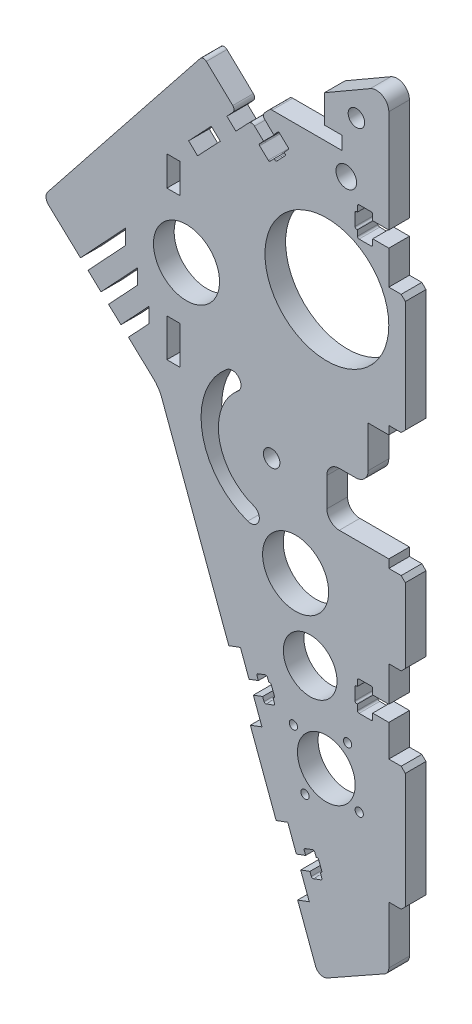
SolidWorks part; units mm, degrees
ref_plane "前视基准面" through (0, 0, 0) normal (0, 0, 1) x (1, 0, 0)
ref_plane "上视基准面" through (0, 0, 0) normal (0, 1, 0) x (1, 0, 0)
ref_plane "右视基准面" through (0, 0, 0) normal (1, 0, 0) x (0, 0, -1)
sketch "草图1" plane through (0, 0, 0) normal (0, 0, 1) x (1, 0, 0)
  line L0 (-10.2785, 30.2586) -> (-10.2785, 20.2586)
  line L1 (-13.2785, 20.2586) -> (-13.2785, 30.2586)
  line L2 (-10.2785, 20.2586) -> (-13.2785, 20.2586)
  line L3 (-13.2785, 30.2586) -> (-10.2785, 30.2586)
  line L4 (-10.2785, 63.2586) -> (-10.2785, 56.2586)
  line L5 (-13.2785, 56.2586) -> (-13.2785, 63.2586)
  line L6 (-13.2785, 56.2586) -> (-10.2785, 56.2586)
  line L7 (-10.2785, 63.2586) -> (-13.2785, 63.2586)
  line L8 (0.0584, 10.1694) -> (8.4478, 4.7272)
  line L9 (8.4478, 4.7272) -> (6.8151, 2.2104)
  line L10 (6.8151, 2.2104) -> (-1.5743, 7.6526)
  line L11 (-1.5743, 7.6526) -> (0.0584, 10.1694)
  line L12 (31.9832, -14.1164) -> (19.3992, -5.953)
  line L13 (19.3992, -5.953) -> (21.0318, -3.4362)
  line L14 (21.0318, -3.4362) -> (33.6159, -11.5996)
  line L15 (33.6159, -11.5996) -> (31.9832, -14.1164)
  line L16 (31.6744, 21.8979) -> (31.6744, -0.3482)
  line L17 (25.0756, 23.4255) -> (27.307, 24.5682)
  line L18 (6.079, 27.2365) -> (23.0089, 23.1784)
  line L19 (27.0417, -2.865) -> (3.747, 12.2464)
  line L20 (2.3797, 14.7633) -> (2.3797, 24.3191)
  line L21 (24.1101, 85.2586) -> (24.1101, 81.2586)
  line L22 (24.1101, 81.2586) -> (25.5101, 81.2586)
  line L23 (25.8101, 80.9586) -> (25.8101, 78.0586)
  line L24 (25.5101, 77.7586) -> (24.0601, 77.7586)
  line L25 (24.0601, 77.7586) -> (24.0601, 77.4586)
  line L26 (23.7601, 77.1586) -> (20.8601, 77.1586)
  line L27 (20.5601, 77.4586) -> (20.5601, 77.7586)
  line L28 (20.5601, 77.7586) -> (19.1101, 77.7586)
  line L29 (18.8101, 78.0586) -> (18.8101, 80.9586)
  line L30 (19.1101, 81.2586) -> (20.5101, 81.2586)
  line L31 (20.5101, 81.2586) -> (20.5101, 85.2586)
  line L32 (20.5101, 85.2586) -> (11.6643, 85.2586)
  line L33 (11.6643, 85.2586) -> (9.5983, 83.0749)
  line L34 (9.5983, 83.0749) -> (12.504, 80.3259)
  line L35 (12.504, 80.3259) -> (13.4662, 81.3429)
  line L36 (13.8903, 81.3547) -> (15.9969, 79.3617)
  line L37 (16.0087, 78.9376) -> (15.0122, 77.8843)
  line L38 (15.0122, 77.8843) -> (15.2301, 77.6781)
  line L39 (15.2419, 77.254) -> (13.2489, 75.1473)
  line L40 (12.8248, 75.1356) -> (12.6068, 75.3417)
  line L41 (12.6068, 75.3417) -> (11.6104, 74.2884)
  line L42 (11.1863, 74.2767) -> (9.0796, 76.2696)
  line L43 (9.0678, 76.6937) -> (10.03, 77.7108)
  line L44 (10.03, 77.7108) -> (7.1242, 80.4597)
  line L45 (7.1242, 80.4597) -> (3.3349, 76.4543)
  line L46 (3.3349, 76.4543) -> (1.1556, 78.516)
  line L47 (1.1556, 78.516) -> (3.2882, 80.7702)
  line L48 (3.2882, 80.7702) -> (-4.6274, 88.2586)
  line L49 (-4.6274, 88.2586) -> (-43.3726, 39.5134)
  line L50 (-43.3726, 39.5134) -> (-15.2785, 13.2991)
  line L51 (-15.2785, 13.2991) -> (23.442, -91.2586)
  line L52 (23.442, -91.2586) -> (40.3726, -81.7414)
  line L53 (40.3726, -81.7414) -> (40.3726, -66.7414)
  line L54 (40.3726, -66.7414) -> (43.3726, -66.7414)
  line L55 (43.3726, -66.7414) -> (43.3726, -36.7414)
  line L56 (43.3726, -36.7414) -> (40.3726, -36.7414)
  line L57 (40.3726, -36.7414) -> (40.3726, -16.7414)
  line L58 (40.3726, -16.7414) -> (43.3726, -16.7414)
  line L59 (43.3726, -16.7414) -> (43.3726, 3.2586)
  line L60 (43.3726, 3.2586) -> (40.3726, 3.2586)
  line L61 (40.3726, 3.2586) -> (40.3726, 33.2586)
  line L62 (40.3726, 33.2586) -> (43.3726, 33.2586)
  line L63 (43.3726, 33.2586) -> (43.3726, 63.2586)
  line L64 (43.3726, 63.2586) -> (40.3726, 63.2586)
  line L65 (40.3726, 63.2586) -> (40.3726, 91.2586)
  line L66 (40.3726, 91.2586) -> (26.0184, 89.2586)
  line L67 (26.0184, 89.2586) -> (26.0184, 88.2586)
  line L68 (26.0184, 88.2586) -> (29.0184, 88.2586)
  line L69 (29.0184, 88.2586) -> (29.0184, 85.2586)
  line L70 (29.0184, 85.2586) -> (24.1101, 85.2586)
  circle A0 centre (-0.6274, 42.9051) radius 1.5
  circle A1 centre (-16.6274, 42.9051) radius 1.5
  circle A2 centre (-8.6274, 42.9051) radius 2
  circle A3 centre (-8.6274, 33.4051) radius 1.5
  circle A4 centre (-8.6274, 52.4051) radius 1.5
  circle A5 centre (-3.3341, -7.5541) radius 1.5
  arc A6 (25.8101, 80.9586) -> (25.5101, 81.2586) centre (25.5101, 80.9586) ccw
  arc A7 (25.5101, 77.7586) -> (25.8101, 78.0586) centre (25.5101, 78.0586) ccw
  arc A8 (23.7601, 77.1586) -> (24.0601, 77.4586) centre (23.7601, 77.4586) ccw
  arc A9 (20.5601, 77.4586) -> (20.8601, 77.1586) centre (20.8601, 77.4586) ccw
  arc A10 (18.8101, 78.0586) -> (19.1101, 77.7586) centre (19.1101, 78.0586) ccw
  arc A11 (19.1101, 81.2586) -> (18.8101, 80.9586) centre (19.1101, 80.9586) ccw
  arc A12 (13.8903, 81.3547) -> (13.4662, 81.3429) centre (13.6841, 81.1367) ccw
  arc A13 (16.0087, 78.9376) -> (15.9969, 79.3617) centre (15.7907, 79.1438) ccw
  arc A14 (15.2419, 77.254) -> (15.2301, 77.6781) centre (15.0239, 77.4602) ccw
  arc A15 (12.8248, 75.1356) -> (13.2489, 75.1473) centre (13.031, 75.3535) ccw
  arc A16 (11.1863, 74.2767) -> (11.6104, 74.2884) centre (11.3924, 74.4946) ccw
  arc A17 (9.0678, 76.6937) -> (9.0796, 76.2696) centre (9.2858, 76.4876) ccw
  circle A18 centre (17.4285, -66.9467) radius 1.5
  circle A19 centre (7.9032, -39.3932) radius 1.5
  arc A20 (27.0417, -2.865) -> (31.6744, -0.3482) centre (28.6744, -0.3482) ccw
  arc A21 (31.6744, 21.8979) -> (27.307, 24.5682) centre (28.6744, 21.8979) ccw
  arc A22 (23.0089, 23.1784) -> (25.0756, 23.4255) centre (23.7082, 26.0958) ccw
  arc A23 (2.3797, 14.7633) -> (3.747, 12.2464) centre (5.3797, 14.7633) ccw
  arc A24 (6.079, 27.2365) -> (2.3797, 24.3191) centre (5.3797, 24.3191) ccw
extrude "凸台-拉伸1" add sketch "草图1" along normal blind 5
sketch "草图2" plane through (0, 0, 5) normal (0, 0, 1) x (1, 0, 0)
  line L0 (16.0872, 85.2586) -> (19.9404, 70.4407)
  line L1 (20.5101, 85.2586) -> (11.6643, 85.2586) construction
  line L2 (19.9404, 70.4407) -> (29.7785, 72.999)
  line L3 (29.7785, 72.999) -> (25.9385, 85.2586)
  line L4 (29.0184, 85.2586) -> (24.1101, 85.2586) construction
  line L5 (25.9385, 85.2586) -> (16.0872, 85.2586)
extrude "凸台-拉伸2" add sketch "草图2" against normal up to surface (5 mm away) up to face at (26.5075, -8.7763, 0)
sketch "草图3" plane through (0, 63.2586, 0) normal (0, 1, 0) x (1, 0, 0)
  line L4 (43.3726, 0) -> (40.3726, 0)
  line L5 (40.3726, 0) -> (40.3726, -5)
  line L6 (40.3726, -5) -> (43.3726, -5)
  line L7 (43.3726, -5) -> (43.3726, 0)
  line L8 (43.3726, 0) -> (40.3726, 0)
  line L9 (40.3726, 0) -> (40.3726, -5)
  line L10 (40.3726, -5) -> (43.3726, -5)
  line L11 (43.3726, -5) -> (43.3726, 0)
  dimension "D1" = 0
extrude "切除-拉伸1" cut sketch "草图3" against normal blind 6
extrude "切除-拉伸2" cut sketch "草图4" against normal blind 5
sketch "草图4" plane through (247.8726, 71.6626, 0) normal (0, 0, -1) x (-1, 0, 0)
  line L24 (211.5, -1.1166) -> (211.5, -2.5166)
  line L25 (207.5, -1.1166) -> (211.5, -1.1166)
  line L26 (207.5, 2.4834) -> (207.5, -1.1166)
  line L27 (211.5, 2.4834) -> (207.5, 2.4834)
  line L28 (211.5, 3.8834) -> (211.5, 2.4834)
  line L29 (214.7, 4.1834) -> (211.8, 4.1834)
  line L30 (215, 2.4334) -> (215, 3.8834)
  line L31 (215.3, 2.4334) -> (215, 2.4334)
  line L32 (215.6, -0.7666) -> (215.6, 2.1334)
  line L33 (215, -1.0666) -> (215.3, -1.0666)
  line L34 (215, -2.5166) -> (215, -1.0666)
  line L35 (211.8, -2.8166) -> (214.7, -2.8166)
  line L48 (215, -102.0074) -> (215, -100.5574)
  line L49 (211.8, -102.3074) -> (214.7, -102.3074)
  line L50 (211.5, -100.6074) -> (211.5, -102.0074)
  line L51 (207.5, -100.6074) -> (211.5, -100.6074)
  line L52 (207.5, -97.0074) -> (207.5, -100.6074)
  line L53 (211.5, -97.0074) -> (207.5, -97.0074)
  line L54 (211.5, -95.6074) -> (211.5, -97.0074)
  line L55 (214.7, -95.3074) -> (211.8, -95.3074)
  line L56 (215, -97.0574) -> (215, -95.6074)
  line L57 (215.3, -97.0574) -> (215, -97.0574)
  line L58 (215.6, -100.2574) -> (215.6, -97.3574)
  line L59 (215, -100.5574) -> (215.3, -100.5574)
  arc A12 (211.5, -2.5166) -> (211.8, -2.8166) centre (211.8, -2.5166) ccw
  arc A13 (211.8, 4.1834) -> (211.5, 3.8834) centre (211.8, 3.8834) ccw
  arc A14 (215, 3.8834) -> (214.7, 4.1834) centre (214.7, 3.8834) ccw
  arc A15 (215.6, 2.1334) -> (215.3, 2.4334) centre (215.3, 2.1334) ccw
  arc A16 (215.3, -1.0666) -> (215.6, -0.7666) centre (215.3, -0.7666) ccw
  arc A17 (214.7, -2.8166) -> (215, -2.5166) centre (214.7, -2.5166) ccw
  arc A24 (214.7, -102.3074) -> (215, -102.0074) centre (214.7, -102.0074) ccw
  arc A25 (211.5, -102.0074) -> (211.8, -102.3074) centre (211.8, -102.0074) ccw
  arc A26 (211.8, -95.3074) -> (211.5, -95.6074) centre (211.8, -95.6074) ccw
  arc A27 (215, -95.6074) -> (214.7, -95.3074) centre (214.7, -95.6074) ccw
  arc A28 (215.6, -97.3574) -> (215.3, -97.0574) centre (215.3, -97.3574) ccw
  arc A29 (215.3, -100.5574) -> (215.6, -100.2574) centre (215.3, -100.2574) ccw
sketch "草图5" plane through (0, 30.2586, 0) normal (0, -1, 0) x (1, 0, 0)
  line L4 (-13.2785, 0) -> (-10.2785, 0)
  line L5 (-10.2785, 0) -> (-10.2785, 5)
  line L6 (-10.2785, 5) -> (-13.2785, 5)
  line L7 (-13.2785, 5) -> (-13.2785, 0)
  line L8 (-13.2785, 0) -> (-10.2785, 0)
  line L9 (-10.2785, 0) -> (-10.2785, 5)
  line L10 (-10.2785, 5) -> (-13.2785, 5)
  line L11 (-13.2785, 5) -> (-13.2785, 0)
  dimension "D1" = 0
extrude "凸台-拉伸3" add sketch "草图5" along normal blind 1
fillet "圆角1" radius 1 6 edges at (40.3726, 91.2586, 2.5) (11.6643, 85.2586, 2.5) (9.5983, 83.0749, 2.5) (7.1242, 80.4597, 2.5) (3.2882, 80.7702, 2.5) (-4.6274, 88.2586, 2.5)
fillet "圆角2" radius 2 3 edges at (-43.3726, 39.5134, 2.5) (40.3726, -81.7414, 2.5) (23.442, -91.2586, 2.5)
fillet "圆角3" radius 8 1 edges at (-15.2785, 13.2991, 2.5)
fillet "圆角4" radius 0.5 1 edges at (26.0184, 88.2586, 2.5)
fillet "圆角5" radius 0.5 1 edges at (26.0184, 89.2586, 2.5)
extrude "切除-拉伸3" cut sketch "草图6" against normal blind 5
sketch "草图6" plane through (151.9934, -9.1138, 5) normal (0, 0, 1) x (1, 0, 0)
  circle A1 centre (-126.6207, 63.3725) radius 13.9
sketch "草图8" plane through (0, 0, 5) normal (0, 0, 1) x (1, 0, 0)
  circle A0 centre (25.3726, 54.2586) radius 13.9 construction
  circle A1 centre (25.3726, 54.2586) radius 13.9
  circle A2 centre (25.3726, 54.2586) radius 15
extrude "切除-拉伸5" cut sketch "草图8" against normal blind 5
sketch "草图9" plane through (0, 57.2586, 0) normal (0, 1, 0) x (1, 0, 0)
  line L4 (43.3726, -5) -> (43.3726, 0)
  line L5 (43.3726, 0) -> (40.3726, 0)
  line L6 (40.3726, 0) -> (40.3726, -5)
  line L7 (40.3726, -5) -> (43.3726, -5)
  line L8 (43.3726, -5) -> (43.3726, 0)
  line L9 (43.3726, 0) -> (40.3726, 0)
  line L10 (40.3726, 0) -> (40.3726, -5)
  line L11 (40.3726, -5) -> (43.3726, -5)
  dimension "D1" = 0
extrude "凸台-拉伸4" add sketch "草图9" along normal blind 5
sketch "草图10" plane through (0, 0, 5) normal (0, 0, 1) x (1, 0, 0)
  circle A0 centre (-3.0861, 36.5718) radius 2.5
extrude "切除-拉伸6" cut sketch "草图10" against normal blind 7
extrude "切除-拉伸7" cut sketch "草图11" against normal blind 7
sketch "草图11" plane through (151.9934, -9.1138, 0) normal (0, 0, -1) x (-1, 0, 0)
  line L1 (186.3158, 40.1826) -> (175.4002, 51.8809)
  line L3 (175.4002, 48.2164) -> (175.4002, 51.8809)
  line L5 (184.4879, 38.477) -> (175.4002, 48.2164)
  line L7 (181.3365, 35.5365) -> (172.4676, 45.0414)
  line L9 (172.4676, 45.0414) -> (172.4676, 41.3769)
  line L11 (179.5086, 33.8309) -> (172.4676, 41.3769)
  line L13 (174.6882, 29.333) -> (169.6938, 34.6855)
  line L15 (176.5161, 31.0386) -> (169.6938, 38.35)
  line L17 (169.6938, 34.6855) -> (169.6938, 38.35)
  line L18 (174.6882, 29.333) -> (176.5161, 31.0386)
  line L19 (179.5086, 33.8309) -> (181.3365, 35.5365)
  line L20 (184.4879, 38.477) -> (186.3158, 40.1826)
extrude "切除-拉伸9" cut sketch "草图13" against normal blind 5
sketch "草图13" plane through (151.9934, -9.1138, 5) normal (0, 0, 1) x (1, 0, 0)
  line L8 (-129.6207, -18.2971) -> (-129.6207, -8.2971)
  line L9 (-129.6207, -8.2971) -> (-132.6207, -8.2971)
  line L10 (-132.6207, -8.2971) -> (-132.6207, -18.2971)
  line L11 (-132.6207, -18.2971) -> (-129.6207, -18.2971)
  line L16 (-129.6207, -29.2971) -> (-132.6207, -29.2971)
  line L17 (-132.6207, -29.2971) -> (-132.6207, -39.2971)
  line L18 (-132.6207, -39.2971) -> (-129.6207, -39.2971)
  line L19 (-129.6207, -39.2971) -> (-129.6207, -29.2971)
sketch "草图15" plane through (0, 0, 0) normal (0, 0, -1) x (-1, 0, 0)
  line L0 (1.3888, 38.4073) -> (-2.4087, 34.8956)
  line L1 (5.364, 35.5416) -> (3.2325, 30.8288)
  circle A0 centre (3.0861, 36.5718) radius 2.5 construction
  arc A1 (5.364, 35.5416) -> (1.3888, 38.4073) centre (3.0861, 36.5718) ccw
  arc A2 (-2.4087, 34.8956) -> (3.2325, 30.8288) centre (0, 32.2908) ccw
extrude "切除-拉伸11" cut sketch "草图15" against normal through all
sketch "草图16" plane through (0, 0, 0) normal (0, 0, -1) x (-1, 0, 0)
  line L0 (1.3888, 38.4073) -> (-2.4087, 34.8956) construction
  line L1 (1.3888, 38.4073) -> (-2.4087, 34.8956)
  line L2 (3.2325, 30.8288) -> (5.364, 35.5416) construction
  line L3 (3.2325, 30.8288) -> (5.364, 35.5416)
  line L4 (-2.3797, 24.3191) -> (-2.3797, 14.7633) construction
  line L5 (-2.3797, 24.3191) -> (-2.3797, 14.7633)
  line L6 (-3.747, 12.2464) -> (-27.0417, -2.865) construction
  line L7 (-3.747, 12.2464) -> (-27.0417, -2.865)
  line L8 (-23.0089, 23.1784) -> (-6.079, 27.2365) construction
  line L9 (-23.0089, 23.1784) -> (-6.079, 27.2365)
  line L10 (-27.307, 24.5682) -> (-25.0756, 23.4255) construction
  line L11 (-27.307, 24.5682) -> (-25.0756, 23.4255)
  line L12 (-31.6744, -0.3482) -> (-31.6744, 21.8979) construction
  line L13 (-31.6744, -0.3482) -> (-31.6744, 21.8979)
  circle A2 centre (8.6274, 52.4051) radius 1.5 construction
  circle A3 centre (8.6274, 52.4051) radius 1.5
  circle A4 centre (16.6274, 42.9051) radius 1.5 construction
  circle A5 centre (16.6274, 42.9051) radius 1.5
  circle A6 centre (0.6274, 42.9051) radius 1.5 construction
  circle A7 centre (0.6274, 42.9051) radius 1.5
  circle A8 centre (8.6274, 33.4051) radius 1.5 construction
  circle A9 centre (8.6274, 33.4051) radius 1.5
  arc A10 (5.364, 35.5416) -> (1.3888, 38.4073) centre (3.0861, 36.5718) ccw construction
  arc A11 (5.364, 35.5416) -> (1.3888, 38.4073) centre (3.0861, 36.5718) ccw
  arc A12 (-2.4087, 34.8956) -> (3.2325, 30.8288) centre (0, 32.2908) ccw construction
  arc A13 (-2.4087, 34.8956) -> (3.2325, 30.8288) centre (0, 32.2908) ccw
  arc A14 (-2.3797, 24.3191) -> (-6.079, 27.2365) centre (-5.3797, 24.3191) ccw construction
  arc A15 (-2.3797, 24.3191) -> (-6.079, 27.2365) centre (-5.3797, 24.3191) ccw
  arc A16 (-3.747, 12.2464) -> (-2.3797, 14.7633) centre (-5.3797, 14.7633) ccw construction
  arc A17 (-3.747, 12.2464) -> (-2.3797, 14.7633) centre (-5.3797, 14.7633) ccw
  arc A18 (-25.0756, 23.4255) -> (-23.0089, 23.1784) centre (-23.7082, 26.0958) ccw construction
  arc A19 (-25.0756, 23.4255) -> (-23.0089, 23.1784) centre (-23.7082, 26.0958) ccw
  arc A20 (-27.307, 24.5682) -> (-31.6744, 21.8979) centre (-28.6744, 21.8979) ccw construction
  arc A21 (-27.307, 24.5682) -> (-31.6744, 21.8979) centre (-28.6744, 21.8979) ccw
  arc A22 (-31.6744, -0.3482) -> (-27.0417, -2.865) centre (-28.6744, -0.3482) ccw construction
  arc A23 (-31.6744, -0.3482) -> (-27.0417, -2.865) centre (-28.6744, -0.3482) ccw
extrude "凸台-拉伸5" add sketch "草图16" against normal up to surface (5 mm away) up to face at (-1.5654, 34.4623, 5)
sketch "草图17" plane through (0, 0, 0) normal (0, 0, -1) x (-1, 0, 0)
  circle A0 centre (8.6274, 42.9051) radius 2 construction
  circle A1 centre (8.6274, 42.9051) radius 2
  circle A2 centre (8.6274, 42.9051) radius 10.5
extrude "切除-拉伸12" cut sketch "草图17" against normal blind 10
sketch "草图18" plane through (0, 0, 0) normal (0, 0, -1) x (-1, 0, 0)
  line L0 (-19.3726, -17.4109) -> (-19.3726, -27.4109) construction
  line L1 (-19.3726, -17.4109) -> (-19.3726, -27.4109)
  line L2 (-22.3726, -17.4109) -> (-19.3726, -17.4109) construction
  line L3 (-22.3726, -17.4109) -> (-19.3726, -17.4109)
  line L4 (-22.3726, -27.4109) -> (-22.3726, -17.4109) construction
  line L5 (-22.3726, -27.4109) -> (-22.3726, -17.4109)
  line L6 (-19.3726, -27.4109) -> (-22.3726, -27.4109) construction
  line L7 (-19.3726, -27.4109) -> (-22.3726, -27.4109)
  line L8 (-22.3726, -38.4109) -> (-19.3726, -38.4109) construction
  line L9 (-22.3726, -38.4109) -> (-19.3726, -38.4109)
  line L10 (-19.3726, -38.4109) -> (-19.3726, -48.4109) construction
  line L11 (-19.3726, -38.4109) -> (-19.3726, -48.4109)
  line L12 (-22.3726, -48.4109) -> (-22.3726, -38.4109) construction
  line L13 (-22.3726, -48.4109) -> (-22.3726, -38.4109)
  line L14 (-19.3726, -48.4109) -> (-22.3726, -48.4109) construction
  line L15 (-19.3726, -48.4109) -> (-22.3726, -48.4109)
extrude "凸台-拉伸6" add sketch "草图18" against normal up to surface (5 mm away) up to face at (1.8726, 42.9051, 5)
sketch "草图25" plane through (0, 0, 0) normal (0, 0, -1) x (-1, 0, 0)
  circle A0 centre (8.6274, 42.9051) radius 10.5 construction
  circle A1 centre (8.6274, 42.9051) radius 10.5
  circle A2 centre (8.6274, 42.9051) radius 2.5
extrude "凸台-拉伸7" add sketch "草图25" against normal up to surface (5 mm away) up to face at (1.8726, 42.9051, 5)
sketch "草图26" plane through (0, 0, 5) normal (0, 0, 1) x (1, 0, 0)
  line L0 (19.3992, -5.953) -> (31.9832, -14.1164) construction
  line L1 (19.3992, -5.953) -> (31.9832, -14.1164)
  line L2 (33.6159, -11.5996) -> (21.0318, -3.4362) construction
  line L3 (33.6159, -11.5996) -> (21.0318, -3.4362)
  line L4 (21.0318, -3.4362) -> (19.3992, -5.953) construction
  line L5 (21.0318, -3.4362) -> (19.3992, -5.953)
  line L6 (31.9832, -14.1164) -> (33.6159, -11.5996) construction
  line L7 (31.9832, -14.1164) -> (33.6159, -11.5996)
  line L8 (8.4478, 4.7272) -> (0.0584, 10.1694) construction
  line L9 (8.4478, 4.7272) -> (0.0584, 10.1694)
  line L10 (-1.5743, 7.6526) -> (6.8151, 2.2104) construction
  line L11 (-1.5743, 7.6526) -> (6.8151, 2.2104)
  line L12 (0.0584, 10.1694) -> (-1.5743, 7.6526) construction
  line L13 (0.0584, 10.1694) -> (-1.5743, 7.6526)
  line L14 (6.8151, 2.2104) -> (8.4478, 4.7272) construction
  line L15 (6.8151, 2.2104) -> (8.4478, 4.7272)
extrude "凸台-拉伸8" add sketch "草图26" against normal up to surface (5 mm away) up to face at (19.0434, 36.8161, 0)
sketch "草图28" plane through (0, 0, 0) normal (0, 0, -1) x (-1, 0, 0)
  circle A0 centre (8.6274, 42.9051) radius 2.5 construction
  circle A1 centre (8.6274, 42.9051) radius 2.5
  circle A2 centre (8.6274, 42.9051) radius 8
extrude "切除-拉伸14" cut sketch "草图28" against normal through all
extrude "切除-拉伸15" cut sketch "草图29" against normal blind 10
sketch "草图29" plane through (151.9934, -9.1138, 5) normal (0, 0, 1) x (1, 0, 0)
  circle A1 centre (-128.4734, -29.3717) radius 3
extrude "切除-拉伸18" cut sketch "草图32" against normal blind 10
sketch "草图32" plane through (151.9934, -9.1138, 5) normal (0, 0, 1) x (1, 0, 0)
  circle A1 centre (-134.1956, 0.0776) radius 2
sketch "草图33" plane through (0, 0, 5) normal (0, 0, 1) x (1, 0, 0)
  circle A0 centre (23.5199, -38.4855) radius 3 construction
  circle A1 centre (23.5199, -38.4855) radius 3
  circle A2 centre (23.5199, -38.4855) radius 6.5
extrude "切除-拉伸19" cut sketch "草图33" against normal blind 10
sketch "草图34" plane through (0, 0, 5) normal (0, 0, 1) x (1, 0, 0)
  circle A0 centre (17.7978, -9.0362) radius 2 construction
  circle A1 centre (17.7978, -9.0362) radius 2
  circle A2 centre (17.7978, -9.0362) radius 6.5
extrude "切除-拉伸20" cut sketch "草图34" against normal blind 5
extrude "切除-拉伸21" cut sketch "草图35" against normal blind 5
sketch "草图35" plane through (151.9934, -9.1138, 5) normal (0, 0, 1) x (1, 0, 0)
  arc A1 (-148.5764, 31.7235) -> (-144.5725, 8.5963) centre (-139.9995, 21.2982) ccw
  arc A3 (-150.4824, 34.0402) -> (-145.5887, 5.7737) centre (-139.9995, 21.2982) ccw
  arc A5 (-148.5764, 31.7235) -> (-150.4824, 34.0402) centre (-149.5294, 32.8818) ccw
  arc A7 (-145.5887, 5.7737) -> (-144.5725, 8.5963) centre (-145.0806, 7.185) ccw
  circle A9 centre (-139.9995, 21.2982) radius 1.05
sketch "草图36" plane through (0, 0, 5) normal (0, 0, 1) x (1, 0, 0)
  circle A0 centre (11.9939, 12.1844) radius 1.05 construction
  circle A1 centre (11.9939, 12.1844) radius 1.05
  circle A2 centre (11.9939, 12.1844) radius 2.5
extrude "切除-拉伸22" cut sketch "草图36" against normal blind 5
sketch "草图37" plane through (0, 0, 5) normal (0, 0, 1) x (1, 0, 0)
  circle A0 centre (11.9939, 12.1844) radius 2.5 construction
  circle A1 centre (11.9939, 12.1844) radius 2.5
  circle A2 centre (11.9939, 12.1844) radius 2
extrude "凸台-拉伸9" add sketch "草图37" against normal blind 5
sketch "草图38" plane through (0, 0, 5) normal (0, 0, 1) x (1, 0, 0)
  arc A0 (3.417, 22.6097) -> (7.4209, -0.5175) centre (11.9939, 12.1844) ccw construction
  arc A1 (3.417, 22.6097) -> (7.4209, -0.5175) centre (11.9939, 12.1844) ccw
  arc A2 (1.511, 24.9264) -> (6.4046, -3.3401) centre (11.9939, 12.1844) ccw construction
  arc A3 (1.511, 24.9264) -> (6.4046, -3.3401) centre (11.9939, 12.1844) ccw
  arc A4 (3.417, 22.6097) -> (1.511, 24.9264) centre (2.464, 23.768) ccw construction
  arc A5 (3.417, 22.6097) -> (1.511, 24.9264) centre (2.464, 23.768) ccw
  arc A6 (6.4046, -3.3401) -> (7.4209, -0.5175) centre (6.9127, -1.9288) ccw construction
  arc A7 (6.4046, -3.3401) -> (7.4209, -0.5175) centre (6.9127, -1.9288) ccw
  arc A8 (3.7346, 22.2235) -> (7.5902, -0.047) centre (11.9939, 12.1844) ccw
  arc A9 (6.2353, -3.8106) -> (7.5902, -0.047) centre (6.9127, -1.9288) ccw
  arc A10 (1.1933, 25.3125) -> (6.2353, -3.8106) centre (11.9939, 12.1844) ccw
  arc A11 (3.7346, 22.2235) -> (1.1933, 25.3125) centre (2.464, 23.768) ccw
  dimension "D1" = 0.5
extrude "切除-拉伸23" cut sketch "草图38" against normal blind 5
sketch "草图39" plane through (0, 0, 5) normal (0, 0, 1) x (1, 0, 0)
  circle A0 centre (17.7978, -9.0362) radius 6.5 construction
  circle A1 centre (17.7978, -9.0362) radius 6.5
  circle A2 centre (23.5199, -38.4855) radius 6.5 construction
  circle A3 centre (23.5199, -38.4855) radius 6.5
  circle A4 centre (23.5199, -38.4855) radius 8.5
  circle A5 centre (17.7978, -9.0362) radius 8
extrude "切除-拉伸25" cut sketch "草图39" against normal through all
sketch "草图40" plane through (0, 0, 5) normal (0, 0, 1) x (1, 0, 0)
  circle A0 centre (17.4285, -66.9467) radius 1.5 construction
  circle A1 centre (17.4285, -66.9467) radius 1.5
  circle A2 centre (7.9032, -39.3932) radius 1.5 construction
  circle A3 centre (7.9032, -39.3932) radius 1.5
  circle A4 centre (-3.3341, -7.5541) radius 1.5 construction
  circle A5 centre (-3.3341, -7.5541) radius 1.5
extrude "凸台-拉伸10" add sketch "草图40" against normal up to surface (5 mm away) up to face at (32.0199, -38.4855, 0)
extrude "切除-拉伸26" cut sketch "草图41" against normal through all
sketch "草图41" plane through (151.9934, -9.1138, -39) normal (0, 0, -1) x (-1, 0, 0)
  circle A0 centre (121.9217, 89.3986) radius 2.5
sketch "草图42" plane through (0, 0, 5) normal (0, 0, 1) x (1, 0, 0)
  circle A0 centre (23.5199, -38.4855) radius 8.5 construction
  circle A1 centre (23.5199, -38.4855) radius 8.5
extrude "凸台-拉伸11" add sketch "草图42" against normal up to surface (5 mm away) up to face at (32.5717, 80.2848, 0)
extrude "切除-拉伸28" cut sketch "草图44" against normal blind 10
sketch "草图44" plane through (151.9934, -9.1138, 5) normal (0, 0, 1) x (1, 0, 0)
  circle A1 centre (-126.7577, -37.1874) radius 6.95
sketch "草图46" plane through (0, 0, 5) normal (0, 0, 1) x (1, 0, 0)
  circle A4 centre (22.1039, -30.6107) radius 6.5
extrude "切除-拉伸29" cut sketch "草图46" against normal blind 10
sketch "草图47" plane through (0, 0, 5) normal (0, 0, 1) x (1, 0, 0)
  circle A2 centre (22.1039, -30.6107) radius 6.5 construction
  circle A3 centre (22.1039, -30.6107) radius 6.5
  circle A4 centre (17.7978, -9.0362) radius 8 construction
  circle A5 centre (17.7978, -9.0362) radius 8
  circle A6 centre (25.2356, -46.3012) radius 7
extrude "切除-拉伸30" cut sketch "草图47" against normal through all
extrude "切除-拉伸31" cut sketch "草图50" against normal blind 10
sketch "草图50" plane through (151.9934, -9.1138, 0) normal (0, 0, -1) x (-1, 0, 0)
  line L1 (116.6207, 14.3725) -> (116.6207, 40.3725)
  line L3 (111.6207, 14.3725) -> (116.6207, 14.3725)
  line L5 (116.6207, 40.3725) -> (111.6207, 40.3725)
  line L6 (111.6207, 40.3725) -> (111.6207, 14.3725)
extrude "切除-拉伸32" cut sketch "草图51" against normal blind 10
sketch "草图51" plane through (151.9934, -9.1138, 5) normal (0, 0, 1) x (1, 0, 0)
  circle A1 centre (-131.9154, -45.1654) radius 1
  circle A3 centre (-134.7358, -32.0298) radius 1
  circle A5 centre (-118.7797, -42.345) radius 1
  circle A7 centre (-121.6001, -29.2094) radius 1
extrude "切除-拉伸33" cut sketch "草图52" against normal blind 5
sketch "草图52" plane through (151.9934, -9.1138, 0) normal (0, 0, -1) x (-1, 0, 0)
  line L8 (154.6175, 83.6344) -> (152.4382, 81.5727)
  line L9 (152.4382, 81.5727) -> (159.3106, 74.3084)
  line L10 (159.3106, 74.3084) -> (161.4899, 76.3701)
  line L11 (161.4899, 76.3701) -> (154.6175, 83.6344)
sketch "草图54" plane through (29.0913, 30.7505, 0) normal (0.6872, 0.7264, 0) x (0.7264, -0.6872, 0)
  line L4 (-50.1197, 0) -> (-53.1197, 0)
  line L5 (-53.1197, 0) -> (-53.1197, -5)
  line L6 (-53.1197, -5) -> (-50.1197, -5)
  line L7 (-50.1197, -5) -> (-50.1197, 0)
  line L8 (-50.1197, 0) -> (-53.1197, 0)
  line L9 (-53.1197, 0) -> (-53.1197, -5)
  line L10 (-53.1197, -5) -> (-50.1197, -5)
  line L11 (-50.1197, -5) -> (-50.1197, 0)
  dimension "D1" = 0
extrude "凸台-拉伸12" add sketch "草图54" along normal blind 2
sketch "草图55" plane through (0, 0, 0) normal (0, 0, -1) x (-1, 0, 0)
  line L3 (-35.3726, 5.2586) -> (-25.3726, 5.2586)
  line L4 (-25.3726, 5.2586) -> (-25.3726, 17.2586)
  line L5 (-35.3726, 18.2586) -> (-25.3726, 18.2586)
  line L6 (-35.3726, 5.2586) -> (-35.3726, 31.2586) construction
  line L7 (-25.3726, 18.2586) -> (-25.3726, 17.2586)
  line L8 (-35.3726, 18.2586) -> (-35.3726, 5.2586)
extrude "切除-拉伸34" cut sketch "草图55" against normal blind 10
fillet "圆角8" radius 3 2 edges at (25.3726, 5.2586, 2.5) (25.3726, 18.2586, 2.5)
fillet "圆角9" radius 3 1 edges at (35.3726, 18.2586, 2.5)
extrude "切除-拉伸35" cut sketch "草图56" against normal blind 5
sketch "草图56" plane through (151.9934, -9.1138, 5) normal (0, 0, 1) x (1, 0, 0)
  line L8 (-133.703, -68.2338) -> (-130.8897, -67.192)
  line L9 (-130.8897, -67.192) -> (-136.0989, -53.1255)
  line L10 (-136.0989, -53.1255) -> (-138.9122, -54.1674)
  line L11 (-138.9122, -54.1674) -> (-133.703, -68.2338)
  line L16 (-145.1632, -37.2876) -> (-142.3499, -36.2458)
  line L17 (-142.3499, -36.2458) -> (-147.559, -22.1794)
  line L18 (-147.559, -22.1794) -> (-150.3723, -23.2212)
  line L19 (-150.3723, -23.2212) -> (-145.1632, -37.2876)
extrude "切除-拉伸36" cut sketch "草图57" against normal blind 5
sketch "草图57" plane through (151.9934, -9.1138, 5) normal (0, 0, 1) x (1, 0, 0)
  line L1 (-130.6637, -60.6034) -> (-133.0081, -61.4716)
  line L3 (-130.299, -61.5881) -> (-130.6637, -60.6034)
  line L5 (-128.1318, -61.1054) -> (-129.9135, -61.7652)
  line L7 (-128.3366, -59.6883) -> (-127.9546, -60.7199)
  line L9 (-128.1491, -59.6189) -> (-128.3366, -59.6883)
  line L11 (-128.7012, -57.2641) -> (-127.972, -59.2334)
  line L13 (-129.2743, -57.1564) -> (-129.0867, -57.0869)
  line L15 (-129.6563, -56.1248) -> (-129.2743, -57.1564)
  line L17 (-131.8236, -56.6075) -> (-130.0418, -55.9477)
  line L19 (-131.6361, -57.9777) -> (-132.0007, -56.993)
  line L21 (-133.9805, -58.8459) -> (-131.6361, -57.9777)
  line L22 (-133.0081, -61.4716) -> (-133.9805, -58.8459)
  line L24 (-142.1239, -29.6573) -> (-144.4683, -30.5255)
  line L26 (-141.7592, -30.6419) -> (-142.1239, -29.6573)
  line L28 (-139.592, -30.1592) -> (-141.3737, -30.8191)
  line L30 (-139.7968, -28.7422) -> (-139.4148, -29.7737)
  line L32 (-139.6093, -28.6727) -> (-139.7968, -28.7422)
  line L34 (-140.1614, -26.3179) -> (-139.4321, -28.2872)
  line L36 (-140.7345, -26.2102) -> (-140.5469, -26.1408)
  line L38 (-141.1165, -25.1787) -> (-140.7345, -26.2102)
  line L40 (-143.2837, -25.6614) -> (-141.502, -25.0015)
  line L42 (-143.0962, -27.0315) -> (-143.4609, -26.0469)
  line L44 (-145.4407, -27.8997) -> (-143.0962, -27.0315)
  line L45 (-144.4683, -30.5255) -> (-145.4407, -27.8997)
  arc A1 (-130.299, -61.5881) -> (-129.9135, -61.7652) centre (-130.0177, -61.4839) ccw
  arc A3 (-128.1318, -61.1054) -> (-127.9546, -60.7199) centre (-128.236, -60.8241) ccw
  arc A5 (-128.1491, -59.6189) -> (-127.972, -59.2334) centre (-128.2533, -59.3376) ccw
  arc A7 (-128.7012, -57.2641) -> (-129.0867, -57.0869) centre (-128.9826, -57.3682) ccw
  arc A9 (-129.6563, -56.1248) -> (-130.0418, -55.9477) centre (-129.9376, -56.229) ccw
  arc A11 (-131.8236, -56.6075) -> (-132.0007, -56.993) centre (-131.7194, -56.8888) ccw
  arc A13 (-141.7592, -30.6419) -> (-141.3737, -30.8191) centre (-141.4779, -30.5377) ccw
  arc A15 (-139.592, -30.1592) -> (-139.4148, -29.7737) centre (-139.6961, -29.8779) ccw
  arc A17 (-139.6093, -28.6727) -> (-139.4321, -28.2872) centre (-139.7135, -28.3914) ccw
  arc A19 (-140.1614, -26.3179) -> (-140.5469, -26.1408) centre (-140.4427, -26.4221) ccw
  arc A21 (-141.1165, -25.1787) -> (-141.502, -25.0015) centre (-141.3978, -25.2829) ccw
  arc A23 (-143.2837, -25.6614) -> (-143.4609, -26.0469) centre (-143.1796, -25.9427) ccw
sketch "草图58" plane through (0, 0, 0) normal (0, 0, -1) x (-1, 0, 0)
  line L0 (-40.3726, 90.1097) -> (-40.3726, 113.7206)
  line L1 (-40.3726, 113.7206) -> (-17.8467, 113.7206)
  line L2 (-29.0184, 88.2586) -> (-17.8467, 88.2586)
  line L3 (-17.8467, 88.2586) -> (-17.8467, 113.7206)
  line L4 (-40.3726, 90.1097) -> (-40.3726, 88.2586)
  line L5 (-40.3726, 74.146) -> (-40.3726, 90.1097) construction
  line L6 (-40.3726, 88.2586) -> (-29.0184, 88.2586)
extrude "凸台-拉伸13" add sketch "草图58" against normal up to surface (5 mm away) up to face at (18.7681, 10.557, 5)
extrude "切除-拉伸37" cut sketch "草图59" against normal blind 5
sketch "草图59" plane through (151.9934, -9.1138, 0) normal (0, 0, -1) x (-1, 0, 0)
  line L1 (127.2092, 104.3725) -> (127.2092, 97.3725)
  line L3 (116.1207, 110.7744) -> (127.2092, 104.3725)
  line L8 (134.1467, 97.3725) -> (134.1467, 122.8344)
  line L10 (134.1467, 97.3725) -> (127.2092, 97.3725)
  line L12 (134.1467, 122.8344) -> (111.6207, 122.8344)
  line L14 (111.6207, 108.1763) -> (111.6207, 122.8344)
  circle A1 centre (119.4684, 102.9285) radius 2
  arc A3 (116.1207, 110.7744) -> (111.6207, 108.1763) centre (114.6207, 108.1763) ccw
sketch "草图60" plane through (43.3726, 0, 0) normal (1, 0, 0) x (0, 0, -1)
  line L4 (0, 33.2586) -> (0, 62.2586)
  line L5 (0, 62.2586) -> (-5, 62.2586)
  line L6 (-5, 62.2586) -> (-5, 33.2586)
  line L7 (-5, 33.2586) -> (0, 33.2586)
  line L8 (0, 33.2586) -> (0, 62.2586)
  line L9 (0, 62.2586) -> (-5, 62.2586)
  line L10 (-5, 62.2586) -> (-5, 33.2586)
  line L11 (-5, 33.2586) -> (0, 33.2586)
  line L12 (0, -16.7414) -> (0, 3.2586)
  line L13 (0, 3.2586) -> (-5, 3.2586)
  line L14 (-5, 3.2586) -> (-5, -16.7414)
  line L15 (-5, -16.7414) -> (0, -16.7414)
  line L16 (0, -16.7414) -> (0, 3.2586)
  line L17 (0, 3.2586) -> (-5, 3.2586)
  line L18 (-5, 3.2586) -> (-5, -16.7414)
  line L19 (-5, -16.7414) -> (0, -16.7414)
  line L20 (0, -66.7414) -> (0, -36.7414)
  line L21 (0, -36.7414) -> (-5, -36.7414)
  line L22 (-5, -36.7414) -> (-5, -66.7414)
  line L23 (-5, -66.7414) -> (0, -66.7414)
  line L24 (0, -66.7414) -> (0, -36.7414)
  line L25 (0, -36.7414) -> (-5, -36.7414)
  line L26 (-5, -36.7414) -> (-5, -66.7414)
  line L27 (-5, -66.7414) -> (0, -66.7414)
  dimension "D1" = 0
  dimension "D2" = 0
  dimension "D3" = 0
extrude "凸台-拉伸14" add sketch "草图60" along normal blind 1
chamfer "倒角1" distance 1 angle 45 6 edges at (44.3726, -66.7414, 2.5) (44.3726, -36.7414, 2.5) (44.3726, 3.2586, 2.5) (44.3726, -16.7414, 2.5) (44.3726, 33.2586, 2.5) (44.3726, 62.2586, 2.5)
sketch "草图61" plane through (0, 88.2586, 0) normal (0, -1, 0) x (1, 0, 0)
  line L4 (29.0184, 5) -> (24.7842, 5)
  line L5 (24.7842, 5) -> (24.7842, 0)
  line L6 (24.7842, 0) -> (29.0184, 0)
  line L7 (29.0184, 0) -> (29.0184, 5)
  line L8 (29.0184, 5) -> (24.7842, 5)
  line L9 (24.7842, 5) -> (24.7842, 0)
  line L10 (24.7842, 0) -> (29.0184, 0)
  line L11 (29.0184, 0) -> (29.0184, 5)
  dimension "D1" = 0
extrude "切除-拉伸38" cut sketch "草图61" against normal blind 0.2
sketch "草图63" plane through (0, 0, 0) normal (0, 0, -1) x (-1, 0, 0)
  line L1 (13.2785, 63.2586) -> (13.2785, 56.2586) construction
  line L2 (13.2785, 63.2586) -> (13.2785, 56.2586)
  line L3 (10.2785, 63.2586) -> (13.2785, 63.2586) construction
  line L4 (10.2785, 63.2586) -> (13.2785, 63.2586)
  line L5 (13.2785, 56.2586) -> (10.2785, 56.2586) construction
  line L6 (13.2785, 56.2586) -> (10.2785, 56.2586)
  line L7 (10.2785, 56.2586) -> (10.2785, 63.2586) construction
  line L8 (10.2785, 56.2586) -> (10.2785, 63.2586)
  line L9 (13.2785, 29.2586) -> (13.2785, 20.2586) construction
  line L10 (13.2785, 29.2586) -> (13.2785, 20.2586)
  line L11 (13.2785, 29.2586) -> (10.2785, 29.2586) construction
  line L12 (13.2785, 29.2586) -> (10.2785, 29.2586)
  line L13 (10.2785, 20.2586) -> (10.2785, 29.2586) construction
  line L14 (10.2785, 20.2586) -> (10.2785, 29.2586)
  line L15 (13.2785, 20.2586) -> (10.2785, 20.2586) construction
  line L16 (13.2785, 20.2586) -> (10.2785, 20.2586)
  line L17 (-32.8726, 74.096) -> (-32.8726, 75.546) construction
  line L18 (-32.8726, 74.096) -> (-32.8726, 75.546)
  line L19 (-33.1726, 75.846) -> (-36.0726, 75.846) construction
  line L20 (-33.1726, 75.846) -> (-36.0726, 75.846)
  line L21 (-32.2726, 70.896) -> (-32.2726, 73.796) construction
  line L22 (-32.2726, 70.896) -> (-32.2726, 73.796)
  line L23 (-36.3726, 75.546) -> (-36.3726, 74.146) construction
  line L24 (-36.3726, 75.546) -> (-36.3726, 74.146)
  line L25 (-32.5726, 74.096) -> (-32.8726, 74.096) construction
  line L26 (-32.5726, 74.096) -> (-32.8726, 74.096)
  line L27 (-32.8726, 70.596) -> (-32.5726, 70.596) construction
  line L28 (-32.8726, 70.596) -> (-32.5726, 70.596)
  line L29 (-32.8726, 69.146) -> (-32.8726, 70.596) construction
  line L30 (-32.8726, 69.146) -> (-32.8726, 70.596)
  line L31 (-36.0726, 68.846) -> (-33.1726, 68.846) construction
  line L32 (-36.0726, 68.846) -> (-33.1726, 68.846)
  line L33 (-36.3726, 70.546) -> (-36.3726, 69.146) construction
  line L34 (-36.3726, 70.546) -> (-36.3726, 69.146)
  line L35 (-40.3726, 70.546) -> (-36.3726, 70.546) construction
  line L36 (-40.3726, 70.546) -> (-36.3726, 70.546)
  line L37 (-36.3726, 74.146) -> (-40.3726, 74.146) construction
  line L38 (-36.3726, 74.146) -> (-40.3726, 74.146)
  line L39 (-32.2726, -28.5948) -> (-32.2726, -25.6948) construction
  line L40 (-32.2726, -28.5948) -> (-32.2726, -25.6948)
  line L41 (-32.5726, -25.3948) -> (-32.8726, -25.3948) construction
  line L42 (-32.5726, -25.3948) -> (-32.8726, -25.3948)
  line L43 (-32.8726, -25.3948) -> (-32.8726, -23.9448) construction
  line L44 (-32.8726, -25.3948) -> (-32.8726, -23.9448)
  line L45 (-33.1726, -23.6448) -> (-36.0726, -23.6448) construction
  line L46 (-33.1726, -23.6448) -> (-36.0726, -23.6448)
  line L47 (-32.8726, -28.8948) -> (-32.5726, -28.8948) construction
  line L48 (-32.8726, -28.8948) -> (-32.5726, -28.8948)
  line L49 (-32.8726, -30.3448) -> (-32.8726, -28.8948) construction
  line L50 (-32.8726, -30.3448) -> (-32.8726, -28.8948)
  line L51 (-36.0726, -30.6448) -> (-33.1726, -30.6448) construction
  line L52 (-36.0726, -30.6448) -> (-33.1726, -30.6448)
  line L53 (-36.3726, -28.9448) -> (-36.3726, -30.3448) construction
  line L54 (-36.3726, -28.9448) -> (-36.3726, -30.3448)
  line L55 (-40.3726, -28.9448) -> (-36.3726, -28.9448) construction
  line L56 (-40.3726, -28.9448) -> (-36.3726, -28.9448)
  line L57 (-36.3726, -25.3448) -> (-40.3726, -25.3448) construction
  line L58 (-36.3726, -25.3448) -> (-40.3726, -25.3448)
  line L59 (-36.3726, -23.9448) -> (-36.3726, -25.3448) construction
  line L60 (-36.3726, -23.9448) -> (-36.3726, -25.3448)
  line L61 (10.1785, 56.1586) -> (10.1785, 63.3586)
  line L62 (10.1785, 63.3586) -> (13.3785, 63.3586)
  line L63 (13.3785, 63.3586) -> (13.3785, 56.1586)
  line L64 (13.3785, 56.1586) -> (10.1785, 56.1586)
  line L65 (10.1785, 20.1586) -> (10.1785, 29.3586)
  line L66 (13.3785, 29.3586) -> (10.1785, 29.3586)
  line L67 (13.3785, 29.3586) -> (13.3785, 20.1586)
  line L68 (13.3785, 20.1586) -> (10.1785, 20.1586)
  line L69 (-40.3726, 70.446) -> (-36.4726, 70.446)
  line L70 (-36.4726, 70.446) -> (-36.4726, 69.146)
  line L71 (-36.0726, 68.746) -> (-33.1726, 68.746)
  line L72 (-32.7726, 69.146) -> (-32.7726, 70.496)
  line L73 (-32.7726, 70.496) -> (-32.5726, 70.496)
  line L74 (-32.1726, 70.896) -> (-32.1726, 73.796)
  line L75 (-32.5726, 74.196) -> (-32.7726, 74.196)
  line L76 (-32.7726, 74.196) -> (-32.7726, 75.546)
  line L77 (-33.1726, 75.946) -> (-36.0726, 75.946)
  line L78 (-36.4726, 75.546) -> (-36.4726, 74.246)
  line L79 (-36.4726, 74.246) -> (-40.3726, 74.246)
  line L80 (-40.3726, -29.0448) -> (-36.4726, -29.0448)
  line L81 (-36.4726, -29.0448) -> (-36.4726, -30.3448)
  line L82 (-36.0726, -30.7448) -> (-33.1726, -30.7448)
  line L83 (-32.7726, -30.3448) -> (-32.7726, -28.9948)
  line L84 (-32.7726, -28.9948) -> (-32.5726, -28.9948)
  line L85 (-32.1726, -28.5948) -> (-32.1726, -25.6948)
  line L86 (-32.5726, -25.2948) -> (-32.7726, -25.2948)
  line L87 (-32.7726, -25.2948) -> (-32.7726, -23.9448)
  line L88 (-33.1726, -23.5448) -> (-36.0726, -23.5448)
  line L89 (-36.4726, -23.9448) -> (-36.4726, -25.2448)
  line L90 (-36.4726, -25.2448) -> (-40.3726, -25.2448)
  line L91 (-40.3726, 74.246) -> (-40.3726, 74.146)
  line L92 (-40.3726, 70.546) -> (-40.3726, 70.446)
  line L93 (-40.3726, -25.2448) -> (-40.3726, -25.3448)
  line L94 (-40.3726, -28.9448) -> (-40.3726, -29.0448)
  arc A0 (-32.8726, 75.546) -> (-33.1726, 75.846) centre (-33.1726, 75.546) ccw construction
  arc A1 (-32.8726, 75.546) -> (-33.1726, 75.846) centre (-33.1726, 75.546) ccw
  arc A2 (-32.2726, 73.796) -> (-32.5726, 74.096) centre (-32.5726, 73.796) ccw construction
  arc A3 (-32.2726, 73.796) -> (-32.5726, 74.096) centre (-32.5726, 73.796) ccw
  arc A4 (-36.0726, 75.846) -> (-36.3726, 75.546) centre (-36.0726, 75.546) ccw construction
  arc A5 (-36.0726, 75.846) -> (-36.3726, 75.546) centre (-36.0726, 75.546) ccw
  arc A6 (-32.5726, 70.596) -> (-32.2726, 70.896) centre (-32.5726, 70.896) ccw construction
  arc A7 (-32.5726, 70.596) -> (-32.2726, 70.896) centre (-32.5726, 70.896) ccw
  arc A8 (-33.1726, 68.846) -> (-32.8726, 69.146) centre (-33.1726, 69.146) ccw construction
  arc A9 (-33.1726, 68.846) -> (-32.8726, 69.146) centre (-33.1726, 69.146) ccw
  arc A10 (-36.3726, 69.146) -> (-36.0726, 68.846) centre (-36.0726, 69.146) ccw construction
  arc A11 (-36.3726, 69.146) -> (-36.0726, 68.846) centre (-36.0726, 69.146) ccw
  arc A12 (-32.2726, -25.6948) -> (-32.5726, -25.3948) centre (-32.5726, -25.6948) ccw construction
  arc A13 (-32.2726, -25.6948) -> (-32.5726, -25.3948) centre (-32.5726, -25.6948) ccw
  arc A14 (-32.8726, -23.9448) -> (-33.1726, -23.6448) centre (-33.1726, -23.9448) ccw construction
  arc A15 (-32.8726, -23.9448) -> (-33.1726, -23.6448) centre (-33.1726, -23.9448) ccw
  arc A16 (-32.5726, -28.8948) -> (-32.2726, -28.5948) centre (-32.5726, -28.5948) ccw construction
  arc A17 (-32.5726, -28.8948) -> (-32.2726, -28.5948) centre (-32.5726, -28.5948) ccw
  arc A18 (-33.1726, -30.6448) -> (-32.8726, -30.3448) centre (-33.1726, -30.3448) ccw construction
  arc A19 (-33.1726, -30.6448) -> (-32.8726, -30.3448) centre (-33.1726, -30.3448) ccw
  arc A20 (-36.3726, -30.3448) -> (-36.0726, -30.6448) centre (-36.0726, -30.3448) ccw construction
  arc A21 (-36.3726, -30.3448) -> (-36.0726, -30.6448) centre (-36.0726, -30.3448) ccw
  arc A22 (-36.0726, -23.6448) -> (-36.3726, -23.9448) centre (-36.0726, -23.9448) ccw construction
  arc A23 (-36.0726, -23.6448) -> (-36.3726, -23.9448) centre (-36.0726, -23.9448) ccw
  arc A24 (-6.2353, -3.8106) -> (-1.1933, 25.3125) centre (-11.9939, 12.1844) ccw construction
  arc A25 (-6.2353, -3.8106) -> (-1.1933, 25.3125) centre (-11.9939, 12.1844) ccw
  arc A26 (-7.5902, -0.047) -> (-3.7346, 22.2235) centre (-11.9939, 12.1844) ccw construction
  arc A27 (-7.5902, -0.047) -> (-3.7346, 22.2235) centre (-11.9939, 12.1844) ccw
  arc A28 (-7.5902, -0.047) -> (-6.2353, -3.8106) centre (-6.9127, -1.9288) ccw construction
  arc A29 (-7.5902, -0.047) -> (-6.2353, -3.8106) centre (-6.9127, -1.9288) ccw
  arc A30 (-1.1933, 25.3125) -> (-3.7346, 22.2235) centre (-2.464, 23.768) ccw construction
  arc A31 (-1.1933, 25.3125) -> (-3.7346, 22.2235) centre (-2.464, 23.768) ccw
  arc A32 (-36.4726, 69.146) -> (-36.0726, 68.746) centre (-36.0726, 69.146) ccw
  arc A33 (-33.1726, 68.746) -> (-32.7726, 69.146) centre (-33.1726, 69.146) ccw
  arc A34 (-32.5726, 70.496) -> (-32.1726, 70.896) centre (-32.5726, 70.896) ccw
  arc A35 (-32.1726, 73.796) -> (-32.5726, 74.196) centre (-32.5726, 73.796) ccw
  arc A36 (-32.7726, 75.546) -> (-33.1726, 75.946) centre (-33.1726, 75.546) ccw
  arc A37 (-36.0726, 75.946) -> (-36.4726, 75.546) centre (-36.0726, 75.546) ccw
  arc A38 (-7.6241, 0.047) -> (-3.7982, 22.1463) centre (-11.9939, 12.1844) ccw
  arc A39 (-1.1298, 25.3897) -> (-3.7982, 22.1463) centre (-2.464, 23.768) ccw
  arc A40 (-6.2014, -3.9047) -> (-1.1298, 25.3897) centre (-11.9939, 12.1844) ccw
  arc A41 (-7.6241, 0.047) -> (-6.2014, -3.9047) centre (-6.9127, -1.9288) ccw
  arc A42 (-36.4726, -30.3448) -> (-36.0726, -30.7448) centre (-36.0726, -30.3448) ccw
  arc A43 (-33.1726, -30.7448) -> (-32.7726, -30.3448) centre (-33.1726, -30.3448) ccw
  arc A44 (-32.5726, -28.9948) -> (-32.1726, -28.5948) centre (-32.5726, -28.5948) ccw
  arc A45 (-32.1726, -25.6948) -> (-32.5726, -25.2948) centre (-32.5726, -25.6948) ccw
  arc A46 (-32.7726, -23.9448) -> (-33.1726, -23.5448) centre (-33.1726, -23.9448) ccw
  arc A47 (-36.0726, -23.5448) -> (-36.4726, -23.9448) centre (-36.0726, -23.9448) ccw
  dimension "D1" = 0.1
extrude "切除-拉伸39" cut sketch "草图63" against normal blind 9
sketch "草图64" plane through (0, 0, 0) normal (0, 0, -1) x (-1, 0, 0)
  line L0 (-8.8971, -36.1453) -> (-6.5527, -37.0135) construction
  line L1 (-8.8971, -36.1453) -> (-6.5527, -37.0135)
  line L2 (-8.5325, -35.1607) -> (-8.8971, -36.1453) construction
  line L3 (-8.5325, -35.1607) -> (-8.8971, -36.1453)
  line L4 (-10.4914, -34.1153) -> (-8.7096, -34.7752) construction
  line L5 (-10.4914, -34.1153) -> (-8.7096, -34.7752)
  line L6 (-11.2589, -35.324) -> (-10.8769, -34.2925) construction
  line L7 (-11.2589, -35.324) -> (-10.8769, -34.2925)
  line L8 (-11.4464, -35.2546) -> (-11.2589, -35.324) construction
  line L9 (-11.4464, -35.2546) -> (-11.2589, -35.324)
  line L10 (-12.5612, -37.401) -> (-11.8319, -35.4317) construction
  line L11 (-12.5612, -37.401) -> (-11.8319, -35.4317)
  line L12 (-12.1965, -37.856) -> (-12.3841, -37.7865) construction
  line L13 (-12.1965, -37.856) -> (-12.3841, -37.7865)
  line L14 (-12.5785, -38.8875) -> (-12.1965, -37.856) construction
  line L15 (-12.5785, -38.8875) -> (-12.1965, -37.856)
  line L16 (-10.6196, -39.9329) -> (-12.4014, -39.273) construction
  line L17 (-10.6196, -39.9329) -> (-12.4014, -39.273)
  line L18 (-9.8695, -38.7711) -> (-10.2341, -39.7557) construction
  line L19 (-9.8695, -38.7711) -> (-10.2341, -39.7557)
  line L20 (-7.5251, -39.6393) -> (-9.8695, -38.7711) construction
  line L21 (-7.5251, -39.6393) -> (-9.8695, -38.7711)
  line L22 (-20.3573, -67.0915) -> (-18.0129, -67.9597) construction
  line L23 (-20.3573, -67.0915) -> (-18.0129, -67.9597)
  line L24 (-19.9926, -66.1068) -> (-20.3573, -67.0915) construction
  line L25 (-19.9926, -66.1068) -> (-20.3573, -67.0915)
  line L26 (-21.9515, -65.0615) -> (-20.1698, -65.7213) construction
  line L27 (-21.9515, -65.0615) -> (-20.1698, -65.7213)
  line L28 (-22.7191, -66.2702) -> (-22.3371, -65.2386) construction
  line L29 (-22.7191, -66.2702) -> (-22.3371, -65.2386)
  line L30 (-22.9066, -66.2007) -> (-22.7191, -66.2702) construction
  line L31 (-22.9066, -66.2007) -> (-22.7191, -66.2702)
  line L32 (-24.0214, -68.3472) -> (-23.2921, -66.3779) construction
  line L33 (-24.0214, -68.3472) -> (-23.2921, -66.3779)
  line L34 (-23.6567, -68.8021) -> (-23.8443, -68.7327) construction
  line L35 (-23.6567, -68.8021) -> (-23.8443, -68.7327)
  line L36 (-24.0387, -69.8337) -> (-23.6567, -68.8021) construction
  line L37 (-24.0387, -69.8337) -> (-23.6567, -68.8021)
  line L38 (-22.0798, -70.879) -> (-23.8616, -70.2192) construction
  line L39 (-22.0798, -70.879) -> (-23.8616, -70.2192)
  line L40 (-18.9853, -70.5854) -> (-21.3297, -69.7172) construction
  line L41 (-18.9853, -70.5854) -> (-21.3297, -69.7172)
  line L42 (-21.3297, -69.7172) -> (-21.6943, -70.7019) construction
  line L43 (-21.3297, -69.7172) -> (-21.6943, -70.7019)
  line L44 (-7.5598, -39.733) -> (-9.8104, -38.8996)
  line L45 (-9.8104, -38.8996) -> (-10.1404, -39.7904)
  line L46 (-10.6544, -40.0266) -> (-12.4361, -39.3668)
  line L47 (-12.6723, -38.8528) -> (-12.325, -37.915)
  line L48 (-12.325, -37.915) -> (-12.4188, -37.8803)
  line L49 (-12.655, -37.3663) -> (-11.9257, -35.397)
  line L50 (-11.4117, -35.1608) -> (-11.3179, -35.1955)
  line L51 (-11.3179, -35.1955) -> (-10.9707, -34.2578)
  line L52 (-10.4566, -34.0216) -> (-8.6749, -34.6814)
  line L53 (-8.4387, -35.1954) -> (-8.7686, -36.0863)
  line L54 (-8.7686, -36.0863) -> (-6.518, -36.9198)
  line L55 (-19.02, -70.6792) -> (-21.2706, -69.8457)
  line L56 (-21.2706, -69.8457) -> (-21.6005, -70.7366)
  line L57 (-22.1146, -70.9728) -> (-23.8963, -70.313)
  line L58 (-24.1325, -69.799) -> (-23.7852, -68.8612)
  line L59 (-23.7852, -68.8612) -> (-23.879, -68.8265)
  line L60 (-24.1152, -68.3124) -> (-23.3859, -66.3431)
  line L61 (-22.8719, -66.1069) -> (-22.7781, -66.1417)
  line L62 (-22.7781, -66.1417) -> (-22.4308, -65.2039)
  line L63 (-21.9168, -64.9677) -> (-20.1351, -65.6276)
  line L64 (-19.8989, -66.1416) -> (-20.2288, -67.0324)
  line L65 (-20.2288, -67.0324) -> (-17.9782, -67.8659)
  line L66 (-6.5527, -37.0135) -> (-6.518, -36.9198)
  line L67 (-7.5598, -39.733) -> (-7.5251, -39.6393)
  line L68 (-18.0129, -67.9597) -> (-17.9782, -67.8659)
  line L69 (-18.9853, -70.5854) -> (-19.02, -70.6792)
  arc A0 (-8.5325, -35.1607) -> (-8.7096, -34.7752) centre (-8.8138, -35.0565) ccw construction
  arc A1 (-8.5325, -35.1607) -> (-8.7096, -34.7752) centre (-8.8138, -35.0565) ccw
  arc A2 (-10.4914, -34.1153) -> (-10.8769, -34.2925) centre (-10.5955, -34.3967) ccw construction
  arc A3 (-10.4914, -34.1153) -> (-10.8769, -34.2925) centre (-10.5955, -34.3967) ccw
  arc A4 (-11.4464, -35.2546) -> (-11.8319, -35.4317) centre (-11.5506, -35.5359) ccw construction
  arc A5 (-11.4464, -35.2546) -> (-11.8319, -35.4317) centre (-11.5506, -35.5359) ccw
  arc A6 (-12.5612, -37.401) -> (-12.3841, -37.7865) centre (-12.2799, -37.5052) ccw construction
  arc A7 (-12.5612, -37.401) -> (-12.3841, -37.7865) centre (-12.2799, -37.5052) ccw
  arc A8 (-12.5785, -38.8875) -> (-12.4014, -39.273) centre (-12.2972, -38.9917) ccw construction
  arc A9 (-12.5785, -38.8875) -> (-12.4014, -39.273) centre (-12.2972, -38.9917) ccw
  arc A10 (-10.6196, -39.9329) -> (-10.2341, -39.7557) centre (-10.5155, -39.6515) ccw construction
  arc A11 (-10.6196, -39.9329) -> (-10.2341, -39.7557) centre (-10.5155, -39.6515) ccw
  arc A12 (-19.9926, -66.1068) -> (-20.1698, -65.7213) centre (-20.274, -66.0027) ccw construction
  arc A13 (-19.9926, -66.1068) -> (-20.1698, -65.7213) centre (-20.274, -66.0027) ccw
  arc A14 (-21.9515, -65.0615) -> (-22.3371, -65.2386) centre (-22.0557, -65.3428) ccw construction
  arc A15 (-21.9515, -65.0615) -> (-22.3371, -65.2386) centre (-22.0557, -65.3428) ccw
  arc A16 (-22.9066, -66.2007) -> (-23.2921, -66.3779) centre (-23.0108, -66.4821) ccw construction
  arc A17 (-22.9066, -66.2007) -> (-23.2921, -66.3779) centre (-23.0108, -66.4821) ccw
  arc A18 (-24.0214, -68.3472) -> (-23.8443, -68.7327) centre (-23.7401, -68.4514) ccw construction
  arc A19 (-24.0214, -68.3472) -> (-23.8443, -68.7327) centre (-23.7401, -68.4514) ccw
  arc A20 (-24.0387, -69.8337) -> (-23.8616, -70.2192) centre (-23.7574, -69.9379) ccw construction
  arc A21 (-24.0387, -69.8337) -> (-23.8616, -70.2192) centre (-23.7574, -69.9379) ccw
  arc A22 (-22.0798, -70.879) -> (-21.6943, -70.7019) centre (-21.9756, -70.5977) ccw construction
  arc A23 (-22.0798, -70.879) -> (-21.6943, -70.7019) centre (-21.9756, -70.5977) ccw
  arc A24 (-10.6544, -40.0266) -> (-10.1404, -39.7904) centre (-10.5155, -39.6515) ccw
  arc A25 (-12.6723, -38.8528) -> (-12.4361, -39.3668) centre (-12.2972, -38.9917) ccw
  arc A26 (-12.655, -37.3663) -> (-12.4188, -37.8803) centre (-12.2799, -37.5052) ccw
  arc A27 (-11.4117, -35.1608) -> (-11.9257, -35.397) centre (-11.5506, -35.5359) ccw
  arc A28 (-10.4566, -34.0216) -> (-10.9707, -34.2578) centre (-10.5955, -34.3967) ccw
  arc A29 (-8.4387, -35.1954) -> (-8.6749, -34.6814) centre (-8.8138, -35.0565) ccw
  arc A30 (-22.1146, -70.9728) -> (-21.6005, -70.7366) centre (-21.9756, -70.5977) ccw
  arc A31 (-24.1325, -69.799) -> (-23.8963, -70.313) centre (-23.7574, -69.9379) ccw
  arc A32 (-24.1152, -68.3124) -> (-23.879, -68.8265) centre (-23.7401, -68.4514) ccw
  arc A33 (-22.8719, -66.1069) -> (-23.3859, -66.3431) centre (-23.0108, -66.4821) ccw
  arc A34 (-21.9168, -64.9677) -> (-22.4308, -65.2039) centre (-22.0557, -65.3428) ccw
  arc A35 (-19.8989, -66.1416) -> (-20.1351, -65.6276) centre (-20.274, -66.0027) ccw
  dimension "D1" = 0.1
extrude "切除-拉伸40" cut sketch "草图64" against normal blind 9
sketch "草图65" plane through (0, 0, 0) normal (0, 0, -1) x (-1, 0, 0)
  circle A8 centre (-22.1039, -30.6107) radius 6.5 construction
  circle A9 centre (-22.1039, -30.6107) radius 6.5
extrude "凸台-拉伸15" add sketch "草图65" against normal up to surface (5 mm away) up to face at (19.5946, 9.2267, 5)
sketch "草图66" plane through (0, 0, 0) normal (0, 0, -1) x (-1, 0, 0)
  circle A4 centre (-21.321, -26.6881) radius 6.5
extrude "切除-拉伸41" cut sketch "草图66" against normal blind 10
